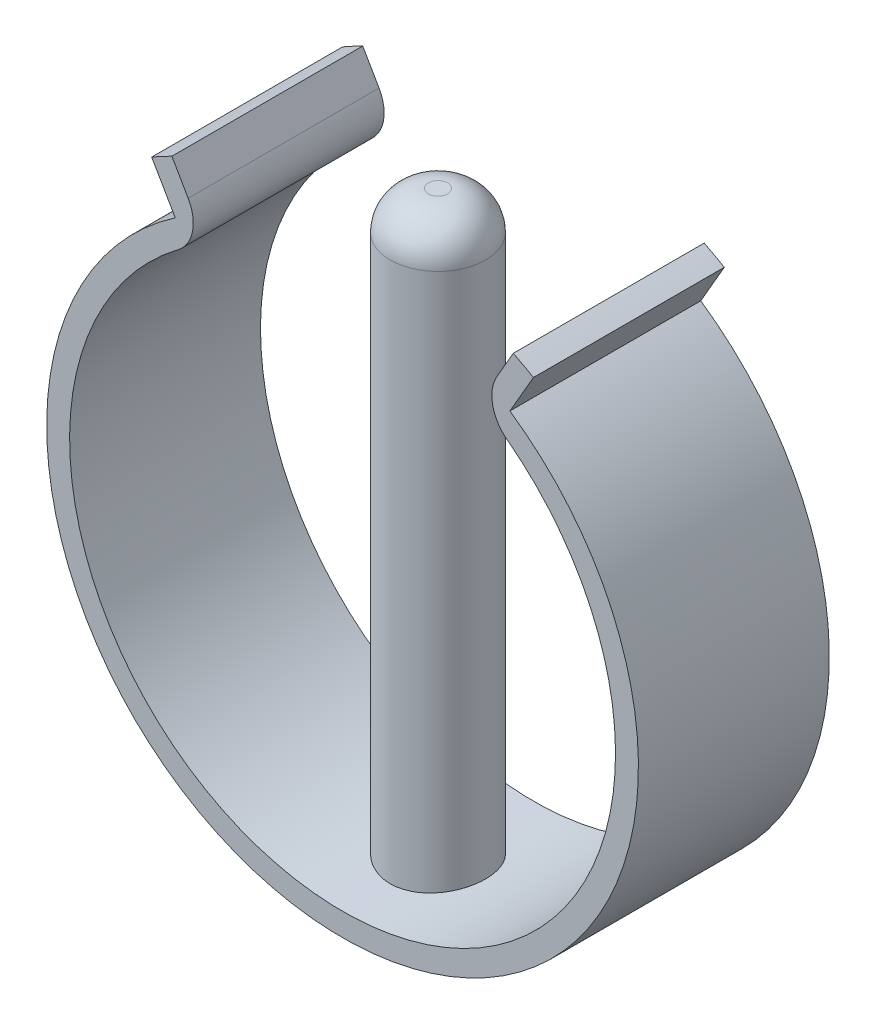
SolidWorks part; units mm, degrees
ref_plane "Front Plane" through (0, 0, 0) normal (0, 0, 1) x (1, 0, 0)
ref_plane "Top Plane" through (0, 0, 0) normal (0, 1, 0) x (1, 0, 0)
ref_plane "Right Plane" through (0, 0, 0) normal (1, 0, 0) x (0, 0, -1)
sketch "Sketch1" plane through (0, 0, 0) normal (0, 0, 1) x (1, 0, 0)
  line L1 (7.15, 12.3842) -> (8.9428, 15.4893)
  line L2 (-7.15, 12.3842) -> (-8.9428, 15.4893)
  line L3 (-8.766, 12.7831) -> (-10, 14.9205)
  line L4 (8.766, 12.7831) -> (10, 14.9205)
  line L5 (0, -2.4) -> (-14.6698, 23.0089) construction
  line L6 (0, 0) -> (-13.6306, 23.6089) construction
  line L7 (0, 0) -> (13.476, 23.3411) construction
  line L8 (0, -2.4) -> (14.5152, 22.7411) construction
  arc A0 (-7.15, 12.3842) -> (7.15, 12.3842) centre (0, 0) ccw
  arc A1 (-8.766, 12.7831) -> (8.766, 12.7831) centre (0, 0) ccw
  arc A2 (10, 14.9205) -> (8.9428, 15.4893) centre (0, -2.4) ccw
  arc A3 (-8.9428, 15.4893) -> (-10, 14.9205) centre (0, -2.4) ccw
  circle A4 centre (0, 0) radius 15.5 construction
  circle A5 centre (0, 0) radius 14.3 construction
  dimension "D1" = 1.2
  dimension "D4" = 1.2
extrude "Boss-Extrude1" add sketch "Sketch1" along normal blind 5 and the other way blind 5
sketch "Sketch2" plane through (0, 0, 0) normal (0, 1, 0) x (1, 0, 0)
  circle A0 centre (0, 0) radius 2.5
extrude "Boss-Extrude2" add sketch "Sketch2" along normal blind 16 and the other way up to next
fillet "Fillet2" radius 2 1 edges at (0, 16, 2.5)
fillet "Fillet3" radius 2 2 edges at (7.15, 12.3842, 0) (-7.15, 12.3842, 0)
